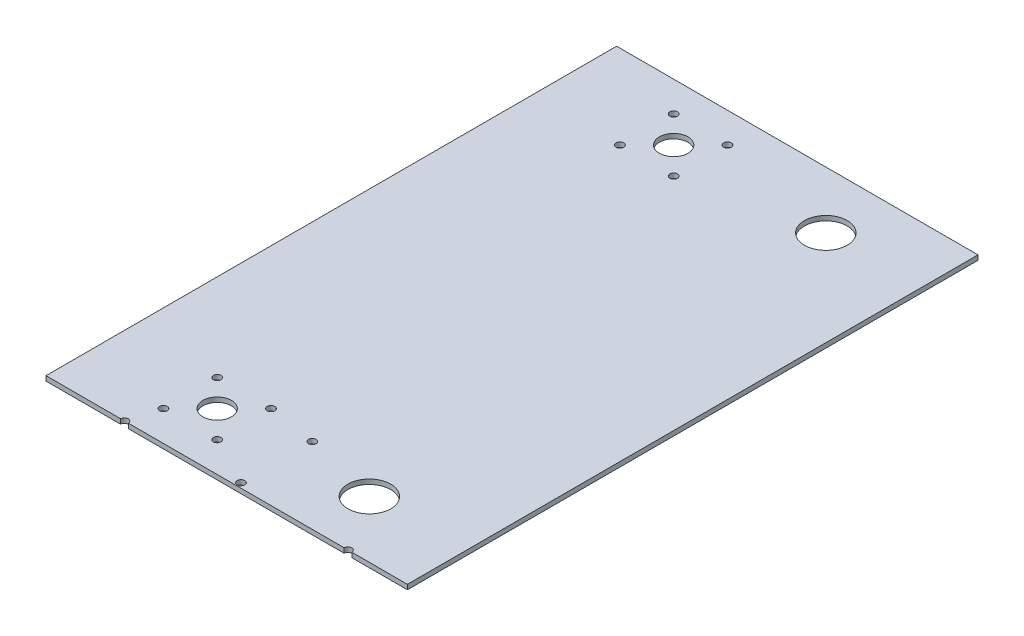
SolidWorks part; units mm, degrees
material "6061-T6 (SS)"
ref_plane "Front Plane" through (0, 0, 0) normal (0, 0, 1) x (1, 0, 0)
ref_plane "Top Plane" through (0, 0, 0) normal (0, 1, 0) x (1, 0, 0)
ref_plane "Right Plane" through (0, 0, 0) normal (1, 0, 0) x (0, 0, -1)
sketch "Sketch1" plane through (0, 0, 0) normal (0, 1, 0) x (1, 0, 0)
  line L1 (120.65, -190.5) -> (-120.65, -190.5)
  line L2 (120.65, -190.5) -> (120.65, 190.5)
  line L3 (120.65, 190.5) -> (-120.65, 190.5)
  line L4 (-120.65, -190.5) -> (-120.65, 190.5)
  line L5 (120.65, -190.5) -> (-120.65, 190.5) construction
  line L6 (120.65, 190.5) -> (-120.65, -190.5) construction
  point P0 (0, 0)
  dimension "D1" = 241.3
  dimension "D2" = 381
extrude "Boss-Extrude1" add sketch "Sketch1" along normal blind 3.175
sketch "Sketch6" plane through (0, 3.175, 0) normal (0, 1, 0) x (1, 0, 0)
  line L1 (-44.45, 152.4) -> (0, 0) construction
  line L2 (0, 0) -> (-44.45, -152.4) construction
  line L5 (-120.65, 190.5) -> (-120.65, -190.5) construction
  circle A0 centre (-44.45, -152.4) radius 38.1 construction
  circle A1 centre (-44.45, 152.4) radius 38.1 construction
  circle A2 centre (57.15, -152.4) radius 38.1 construction
  circle A3 centre (57.15, 152.4) radius 38.1 construction
  dimension "D1" = 76.2
  dimension "D5" = 228.6
  dimension "D3" = 101.6
  dimension "D4" = 76.2
sketch "Sketch7" plane through (0, 3.175, 0) normal (0, 1, 0) x (1, 0, 0)
  circle A0 centre (57.15, -152.4) radius 14.2875
  circle A1 centre (57.15, 152.4) radius 14.2875
  circle A2 centre (-44.45, 152.4) radius 9.525
  circle A3 centre (-44.45, -152.4) radius 9.525
  circle A4 centre (-62.4105, 170.3605) radius 2.5527
  circle A5 centre (-44.45, 152.4) radius 25.4 construction
  circle A6 centre (-26.4895, 170.3605) radius 2.5527
  circle A7 centre (-26.4895, 134.4395) radius 2.5527
  circle A8 centre (-62.4105, 134.4395) radius 2.5527
  circle A9 centre (-44.45, -152.4) radius 25.4 construction
  circle A10 centre (-62.4105, -134.4395) radius 2.5527
  circle A11 centre (-26.4895, -134.4395) radius 2.5527
  circle A12 centre (-26.4895, -170.3605) radius 2.5527
  circle A13 centre (-62.4105, -170.3605) radius 2.5527
  point P24 (-44.45, 152.4)
  point P34 (-44.45, -152.4)
  dimension "D1" = 28.575
  dimension "D2" = 19.05
  dimension "D3" = 5.1054
  dimension "D5" = 50.8
  dimension "D4" = 4
  dimension "D6" = 4
extrude "Axle Holes" cut sketch "Sketch7" against normal through all
sketch "Sketch10" plane through (0, 3.175, 0) normal (0, 1, 0) x (1, 0, 0)
  circle A0 centre (6.35, -139.7) radius 2.5527 construction
  circle A1 centre (-68.2625, -190.5) radius 2.5527 construction
  circle A3 centre (6.35, -187.325) radius 2.5527 construction
  circle A4 centre (80.9625, -190.5) radius 2.5527 construction
  circle A5 centre (6.35, -139.7) radius 2.5527
  circle A6 centre (-68.2625, -190.5) radius 2.5527
  circle A8 centre (6.35, -187.325) radius 2.5527
  circle A9 centre (80.9625, -190.5) radius 2.5527
extrude "Cut-Extrude5" cut sketch "Sketch10" against normal through all
sketch "Sketch8" plane through (0, 3.175, 0) normal (0, 1, 0) x (1, 0, 0)
  circle A3 centre (38.8835, 28.8822) radius 19.8684
extrude "Cut-Extrude4" [suppressed] cut sketch "Sketch8" against normal through all
